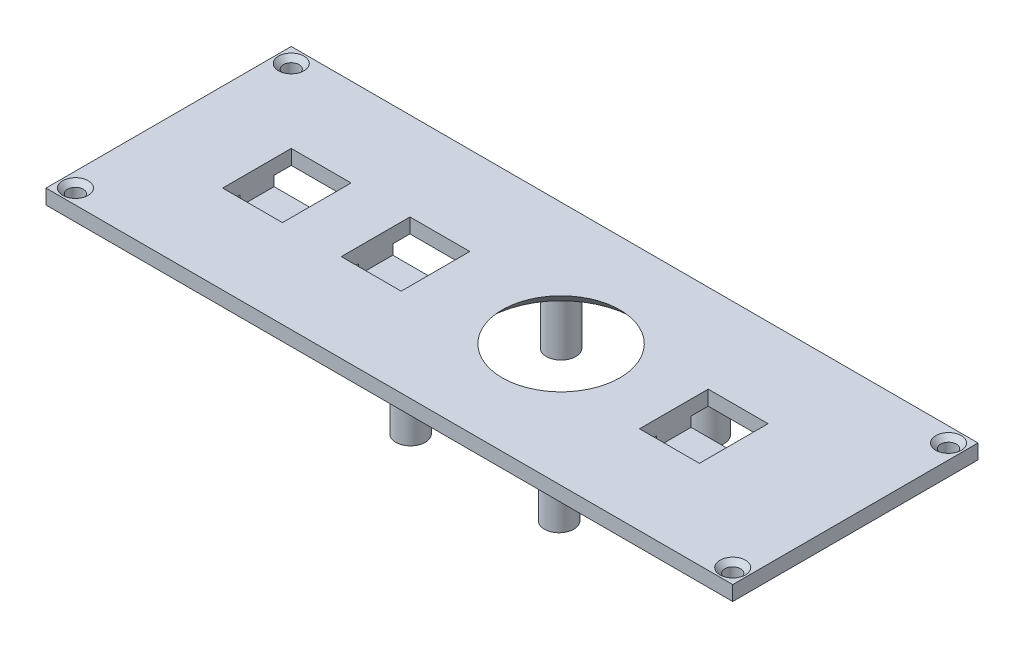
SolidWorks part; units mm, degrees
ref_plane "Front Plane" through (0, 0, 0) normal (0, 0, 1) x (1, 0, 0)
ref_plane "Top Plane" through (0, 0, 0) normal (0, 1, 0) x (1, 0, 0)
ref_plane "Right Plane" through (0, 0, 0) normal (1, 0, 0) x (0, 0, -1)
sketch "Sketch1" plane through (0, 0, 0) normal (0, 1, 0) x (1, 0, 0)
  line L1 (-44.9721, 17.6676) -> (95.0279, 17.6676)
  line L2 (-44.9721, 17.6676) -> (-44.9721, -32.3324)
  line L3 (-44.9721, -32.3324) -> (95.0279, -32.3324)
  line L4 (95.0279, 17.6676) -> (95.0279, -32.3324)
  dimension "D1" = 50
  dimension "D2" = 140
extrude "Boss-Extrude1" add sketch "Sketch1" along normal blind 3
sketch "Sketch2" plane through (0, 3, 0) normal (0, 1, 0) x (1, 0, 0)
  line L0 (95.0279, 17.6676) -> (-44.9721, 17.6676) construction
  line L1 (-44.9721, 17.6676) -> (-44.9721, -32.3324) construction
  line L2 (95.0279, -32.3324) -> (95.0279, 17.6676) construction
  circle A0 centre (-41.9721, 14.6676) radius 1.6
  circle A1 centre (92.0279, 14.6676) radius 1.6
  circle A2 centre (-41.9721, -29.3324) radius 1.6
  circle A3 centre (92.0279, -29.3324) radius 1.6
  dimension "D1" = 3
  dimension "D2" = 3
  dimension "D3" = 3
  dimension "D4" = 3.2
  dimension "D5" = 3.2
  dimension "D6" = 2
extrude "Cut-Extrude1" cut sketch "Sketch2" against normal blind 3
sketch "Sketch3" plane through (0, 3, 0) normal (0, 1, 0) x (1, 0, 0)
  line L0 (95.0279, -32.3324) -> (95.0279, 17.6676) construction
  circle A0 centre (35.0279, -7.3324) radius 12
  dimension "D1" = 60
  dimension "D2" = 24
extrude "Cut-Extrude2" cut sketch "Sketch3" against normal blind 3
chamfer "Chamfer1" distance 1 angle 45 4 edges at (92.0279, 3, 30.9324) (92.0279, 3, -13.0676) (-41.9721, 3, 30.9324) (-41.9721, 3, -13.0676)
chamfer "Chamfer2" distance 3 angle 45 1 edges at (35.0279, 0, 19.3324)
sketch "Sketch4" plane through (0, 0, 0) normal (0, -1, 0) x (1, 0, 0)
  circle A0 centre (19.7879, -7.9076) radius 3
  circle A1 centre (35.0279, 7.3324) radius 15 construction
  circle A2 centre (19.7879, -7.9076) radius 1.45
  circle A3 centre (19.5879, 22.5724) radius 1.45
  circle A4 centre (19.5879, 22.5724) radius 3
  circle A5 centre (50.0679, 22.7724) radius 1.45
  circle A6 centre (50.0679, 22.7724) radius 3
  circle A7 centre (50.2679, -7.7076) radius 1.45
  circle A8 centre (50.2679, -7.7076) radius 3
  point P17 (34.9279, 7.4324)
  dimension "D1" = 15.24
  dimension "D2" = 15.24
  dimension "D3" = 6
  dimension "D4" = 2.9
  dimension "D5" = 4
extrude "Boss-Extrude2" add sketch "Sketch4" along normal blind 13
fillet "Fillet1" radius 2 4 edges at (19.7879, 0, -4.9076) (19.5879, 0, 25.5724) (50.0679, 0, 25.7724) (50.2679, 0, -4.7076)
sketch "Sketch5" plane through (0, 3, 0) normal (0, 1, 0) x (1, 0, 0)
  line L0 (-44.9721, -32.3324) -> (95.0279, -32.3324) construction
  line L1 (-26.9721, -0.3324) -> (-14.7721, -0.3324)
  line L2 (-26.9721, -0.3324) -> (-26.9721, -14.3324)
  line L3 (-26.9721, -14.3324) -> (-14.7721, -14.3324)
  line L4 (-14.7721, -0.3324) -> (-14.7721, -14.3324)
  line L5 (-44.9721, 17.6676) -> (-44.9721, -32.3324) construction
  line L6 (-2.7721, -0.3324) -> (-2.7721, -14.3324)
  line L7 (-2.7721, -0.3324) -> (9.4279, -0.3324)
  line L8 (9.4279, -0.3324) -> (9.4279, -14.3324)
  line L9 (-2.7721, -14.3324) -> (9.4279, -14.3324)
  line L10 (58.0279, -0.3324) -> (58.0279, -14.3324)
  line L11 (58.0279, -0.3324) -> (70.2279, -0.3324)
  line L12 (70.2279, -0.3324) -> (70.2279, -14.3324)
  line L13 (58.0279, -14.3324) -> (70.2279, -14.3324)
  dimension "D1" = 12.2
  dimension "D2" = 14
  dimension "D3" = 18
  dimension "D4" = 18
  dimension "D5" = 2
  dimension "D6" = 2
extrude "Cut-Extrude3" cut sketch "Sketch5" against normal blind 13
sketch "Sketch6" plane through (0, 0, 0) normal (0, -1, 0) x (1, 0, 0)
  line L0 (-26.9721, 0.3324) -> (-26.9721, 14.3324) construction
  line L1 (-26.9721, 10.8324) -> (-29.9721, 10.8324)
  line L2 (-26.9721, 10.8324) -> (-26.9721, 3.8324)
  line L3 (-26.9721, 3.8324) -> (-29.9721, 3.8324)
  line L4 (-29.9721, 10.8324) -> (-29.9721, 3.8324)
  line L5 (-14.7721, 0.3324) -> (-26.9721, 0.3324) construction
  line L6 (-14.7721, 14.3324) -> (-14.7721, 0.3324) construction
  line L7 (-14.7721, 10.8324) -> (-11.7721, 10.8324)
  line L8 (-14.7721, 10.8324) -> (-14.7721, 3.8324)
  line L9 (-14.7721, 3.8324) -> (-11.7721, 3.8324)
  line L10 (-11.7721, 10.8324) -> (-11.7721, 3.8324)
  line L11 (-2.7721, 10.8324) -> (-2.7721, 3.8324)
  line L12 (-2.7721, 10.8324) -> (-5.7721, 10.8324)
  line L13 (-5.7721, 10.8324) -> (-5.7721, 3.8324)
  line L14 (-2.7721, 3.8324) -> (-5.7721, 3.8324)
  line L15 (9.4279, 10.8324) -> (9.4279, 3.8324)
  line L16 (9.4279, 10.8324) -> (12.4279, 10.8324)
  line L17 (12.4279, 10.8324) -> (12.4279, 3.8324)
  line L18 (9.4279, 3.8324) -> (12.4279, 3.8324)
  line L19 (58.0279, 10.8324) -> (58.0279, 3.8324)
  line L20 (58.0279, 10.8324) -> (55.0279, 10.8324)
  line L21 (55.0279, 10.8324) -> (55.0279, 3.8324)
  line L22 (58.0279, 3.8324) -> (55.0279, 3.8324)
  line L23 (70.2279, 10.8324) -> (70.2279, 3.8324)
  line L24 (70.2279, 10.8324) -> (73.2279, 10.8324)
  line L25 (73.2279, 10.8324) -> (73.2279, 3.8324)
  line L26 (70.2279, 3.8324) -> (73.2279, 3.8324)
  dimension "D1" = 3
  dimension "D2" = 7
  dimension "D3" = 3.5
  dimension "D4" = 3
  dimension "D5" = 2
  dimension "D6" = 2
extrude "Boss-Extrude3" add sketch "Sketch6" along normal blind 2
sketch "Sketch7" plane through (0, -2, 0) normal (0, -1, 0) x (1, 0, 0)
  line L1 (-29.9721, 10.8324) -> (-11.7721, 10.8324)
  line L2 (-29.9721, 10.8324) -> (-29.9721, 3.8324)
  line L3 (-29.9721, 3.8324) -> (-11.7721, 3.8324)
  line L4 (-11.7721, 10.8324) -> (-11.7721, 3.8324)
  line L5 (-5.7721, 10.8324) -> (12.4279, 10.8324)
  line L6 (-5.7721, 10.8324) -> (-5.7721, 3.8324)
  line L7 (-5.7721, 3.8324) -> (12.4279, 3.8324)
  line L8 (12.4279, 10.8324) -> (12.4279, 3.8324)
  line L9 (55.0279, 10.8324) -> (73.2279, 10.8324)
  line L10 (55.0279, 10.8324) -> (55.0279, 3.8324)
  line L11 (55.0279, 3.8324) -> (73.2279, 3.8324)
  line L12 (73.2279, 10.8324) -> (73.2279, 3.8324)
extrude "Boss-Extrude4" add sketch "Sketch7" along normal blind 2
